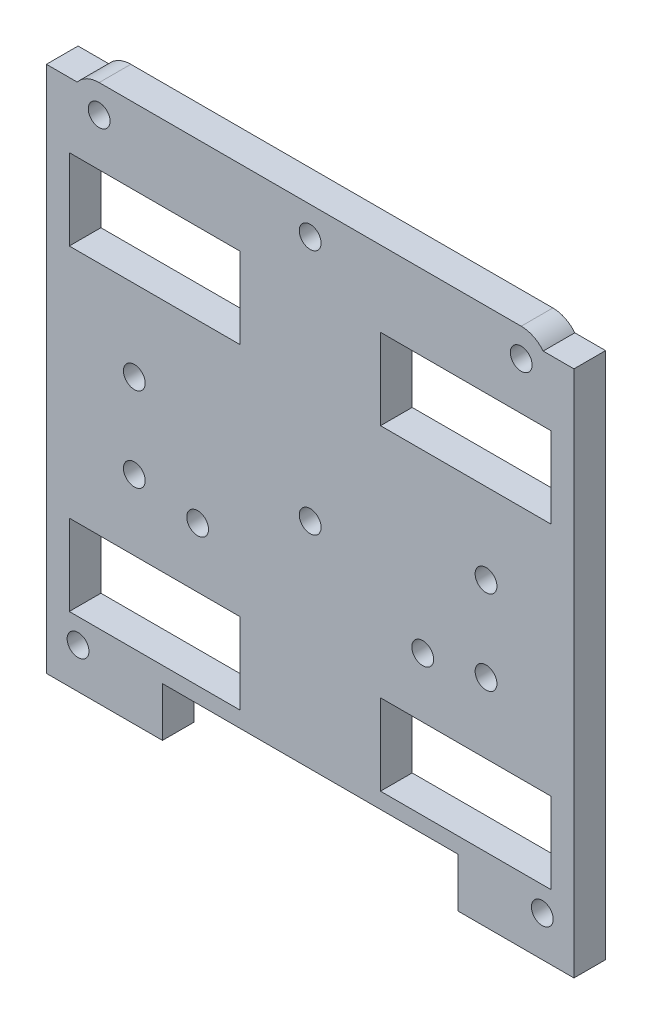
SolidWorks part; units mm, degrees
ref_plane "Front Plane" through (0, 0, 0) normal (0, 0, 1) x (1, 0, 0)
ref_plane "Top Plane" through (0, 0, 0) normal (0, 1, 0) x (1, 0, 0)
ref_plane "Right Plane" through (0, 0, 0) normal (1, 0, 0) x (0, 0, -1)
sketch "Sketch1" plane through (0, 0, 0) normal (0, 0, 1) x (1, 0, 0)
  line L0 (0, -37.5) -> (0, 37.5) construction
  line L1 (-47.5, -37.5) -> (47.5, -37.5)
  line L2 (-47.5, -37.5) -> (-47.5, 37.5)
  line L3 (-47.5, 37.5) -> (47.5, 37.5)
  line L4 (47.5, -37.5) -> (47.5, 37.5)
  line L5 (-47.5, -37.5) -> (47.5, 37.5) construction
  line L6 (-47.5, 37.5) -> (47.5, -37.5) construction
  line L7 (-47.5, 0) -> (47.5, 0) construction
  line L8 (-47.5, 22.5) -> (47.5, 22.5) construction
  line L9 (34.25, 16.75) -> (10, 28.25) construction
  line L10 (-34.25, 28.25) -> (-10, 28.25)
  line L11 (-34.25, 28.25) -> (-34.25, 16.75)
  line L12 (-34.25, 16.75) -> (-10, 16.75)
  line L13 (-10, 28.25) -> (-10, 16.75)
  line L14 (-34.25, 28.25) -> (-10, 16.75) construction
  line L15 (-34.25, 16.75) -> (-10, 28.25) construction
  line L16 (34.25, 28.25) -> (10, 16.75) construction
  line L17 (10, 28.25) -> (10, 16.75)
  line L18 (34.25, 16.75) -> (10, 16.75)
  line L19 (34.25, 28.25) -> (34.25, 16.75)
  line L20 (34.25, 28.25) -> (10, 28.25)
  line L21 (34.25, -28.25) -> (10, -16.75) construction
  line L22 (-34.25, -16.75) -> (-10, -28.25) construction
  line L23 (-34.25, -28.25) -> (-10, -16.75) construction
  line L24 (34.25, -16.75) -> (10, -28.25) construction
  line L25 (34.25, -28.25) -> (10, -28.25)
  line L26 (34.25, -28.25) -> (34.25, -16.75)
  line L27 (34.25, -16.75) -> (10, -16.75)
  line L28 (10, -28.25) -> (10, -16.75)
  line L29 (-10, -28.25) -> (-10, -16.75)
  line L30 (-34.25, -16.75) -> (-10, -16.75)
  line L31 (-34.25, -28.25) -> (-34.25, -16.75)
  line L32 (-34.25, -28.25) -> (-10, -28.25)
  point P0 (0, 0)
  point P12 (-22.125, 22.5)
  point P21 (22.125, 22.5)
  point P30 (22.125, -22.5)
  point P31 (-22.125, -22.5)
  dimension "D1" = 95
  dimension "D2" = 75
  dimension "D3" = 22.5
  dimension "D4" = 24.25
  dimension "D5" = 11.5
  dimension "D6" = 10
extrude "Boss-Extrude1" add sketch "Sketch1" along normal blind 4.5
sketch "Sketch8" plane through (0, 0, 4.5) normal (0, 0, 1) x (1, 0, 0)
  line L0 (-47.5, 37.5) -> (-47.5, -37.5) construction
  line L1 (47.5, -37.5) -> (47.5, 37.5) construction
  circle A0 centre (-47.5, 29.5) radius 8
  circle A1 centre (47.5, 29.5) radius 8
  dimension "D1" = 16
extrude "Boss-Extrude2" [suppressed] add sketch "Sketch8" against normal through all
sketch "Sketch2" plane through (0, 0, 4.5) normal (0, 0, 1) x (1, 0, 0)
  line L0 (0, -37.5) -> (0, 37.5) construction
  line L1 (-47.5, -37.5) -> (47.5, -37.5) construction
  line L2 (47.5, 37.5) -> (-47.5, 37.5) construction
  line L3 (-47.5, 0) -> (47.5, 0) construction
  line L4 (-47.5, 37.5) -> (-47.5, -37.5) construction
  line L5 (47.5, -37.5) -> (47.5, 37.5) construction
  line L6 (-40, 0) -> (40, 0) construction
  line L7 (-30, 35) -> (30, 35) construction
  circle A0 centre (-30, 35) radius 1.55
  circle A1 centre (30, 35) radius 1.55
  circle A2 centre (40, 0) radius 1.55
  circle A3 centre (-40, 0) radius 1.55
  circle A4 centre (0, 35) radius 1.55
  dimension "D1" = 3.1
  dimension "D7" = 3.1
  dimension "D8" = 3.1
  dimension "D9" = 3.1
  dimension "D2" = 30
  dimension "D3" = 35
  dimension "D4" = 80
  dimension "D5" = 40
  dimension "D6" = 0
extrude "screwHoles" cut sketch "Sketch2" against normal through all
sketch "Sketch3" plane through (0, 0, 4.5) normal (0, 0, 1) x (1, 0, 0)
  line L0 (-47.5, -20) -> (26.0486, -20) construction
  line L1 (-47.5, 37.5) -> (-47.5, -37.5) construction
  line L3 (0, 37.5) -> (0, -37.5) construction
  line L4 (47.5, 37.5) -> (-47.5, 37.5) construction
  line L5 (-47.5, -37.5) -> (47.5, -37.5) construction
  line L6 (19.1, -22.35) -> (8.9, -17.65) construction
  line L7 (-19.1, -17.65) -> (-8.9, -17.65)
  line L8 (-19.1, -17.65) -> (-19.1, -22.35)
  line L9 (-19.1, -22.35) -> (-8.9, -22.35)
  line L10 (-8.9, -17.65) -> (-8.9, -22.35)
  line L11 (-19.1, -17.65) -> (-8.9, -22.35) construction
  line L12 (-19.1, -22.35) -> (-8.9, -17.65) construction
  line L13 (19.1, -17.65) -> (8.9, -22.35) construction
  line L14 (8.9, -17.65) -> (8.9, -22.35)
  line L15 (19.1, -22.35) -> (8.9, -22.35)
  line L16 (19.1, -17.65) -> (19.1, -22.35)
  line L17 (19.1, -17.65) -> (8.9, -17.65)
  line L18 (-47.5, 37.5) -> (-47.5, -37.5) construction
  point P2 (-47.5, 0)
  point P12 (-14, -20)
  point P21 (14, -20)
  dimension "D1" = 10.2
  dimension "D2" = 4.7
  dimension "D3" = 14
  dimension "D4" = 20
extrude "BeltClamp" [suppressed] cut sketch "Sketch3" against normal through all
sketch "Sketch4" plane through (0, 0, 4.5) normal (0, 0, 1) x (1, 0, 0)
  line L0 (-47.5, 0) -> (47.5, 0) construction
  line L1 (-47.5, 37.5) -> (-47.5, -37.5) construction
  line L2 (47.5, -37.5) -> (47.5, 37.5) construction
  line L3 (0, 0) -> (0, 33.45) construction
  line L4 (-30.1, 2.35) -> (-19.9, 2.35)
  line L5 (-30.1, 2.35) -> (-30.1, -2.35)
  line L6 (-30.1, -2.35) -> (-19.9, -2.35)
  line L7 (-19.9, 2.35) -> (-19.9, -2.35)
  line L8 (-30.1, 2.35) -> (-19.9, -2.35) construction
  line L9 (-30.1, -2.35) -> (-19.9, 2.35) construction
  line L10 (30.1, -2.35) -> (19.9, 2.35) construction
  line L11 (30.1, 2.35) -> (19.9, -2.35) construction
  line L12 (19.9, 2.35) -> (19.9, -2.35)
  line L13 (30.1, -2.35) -> (19.9, -2.35)
  line L14 (30.1, 2.35) -> (30.1, -2.35)
  line L15 (30.1, 2.35) -> (19.9, 2.35)
  line L16 (-30.1, -2.35) -> (-19.9, 2.35) construction
  circle A0 centre (-40, 0) radius 1.55 construction
  circle A1 centre (0, 35) radius 1.55 construction
  circle A2 centre (0, 0) radius 1.55
  point P6 (-25, 0)
  point P22 (25, 0)
  dimension "D1" = 10.2
  dimension "D2" = 4.7
  dimension "D5" = 3.1
  dimension "D3" = 0
  dimension "D4" = 25
extrude "Cut-Extrude3" cut sketch "Sketch4" against normal through all
sketch "Sketch5" plane through (0, 0, 4.5) normal (0, 0, 1) x (1, 0, 0)
  line L0 (-47.5, -9.75) -> (47.5, -9.75) construction
  line L1 (-47.5, 37.5) -> (-47.5, -37.5) construction
  line L2 (47.5, -37.5) -> (47.5, 37.5) construction
  line L4 (0, -37.5) -> (0, 37.5) construction
  line L5 (-47.5, -37.5) -> (47.5, -37.5) construction
  line L6 (47.5, 37.5) -> (-47.5, 37.5) construction
  line L7 (-30.65, -14.85) -> (-35.35, -4.65) construction
  line L8 (30.65, -4.65) -> (35.35, -4.65)
  line L9 (30.65, -4.65) -> (30.65, -14.85)
  line L10 (30.65, -14.85) -> (35.35, -14.85)
  line L11 (35.35, -4.65) -> (35.35, -14.85)
  line L12 (30.65, -4.65) -> (35.35, -14.85) construction
  line L13 (30.65, -14.85) -> (35.35, -4.65) construction
  line L14 (-30.65, -4.65) -> (-35.35, -14.85) construction
  line L15 (-35.35, -4.65) -> (-35.35, -14.85)
  line L16 (-30.65, -14.85) -> (-35.35, -14.85)
  line L17 (-30.65, -4.65) -> (-30.65, -14.85)
  line L18 (-30.65, -4.65) -> (-35.35, -4.65)
  line L19 (33, -9.75) -> (33, -37.5) construction
  line L20 (-33, -9.75) -> (-33, -37.5) construction
  line L21 (-33, -31.75) -> (33, -31.75) construction
  circle A0 centre (33, -31.75) radius 1.55
  circle A1 centre (-33, -31.75) radius 1.55
  point P15 (33, -9.75)
  point P24 (-33, -9.75)
  dimension "D5" = 3.1
  dimension "D2" = 10.2
  dimension "D3" = 4.7
  dimension "D4" = 33
  dimension "D6" = 22
  dimension "D1" = 9.75
extrude "Cut-Extrude4" cut sketch "Sketch5" against normal through all
sketch "Sketch9" plane through (0, 0, 4.5) normal (0, 0, 1) x (1, 0, 0)
  line L0 (47.5, 37.5) -> (-47.5, 37.5) construction
  line L1 (0, 37.5) -> (0, -37.5) construction
  line L2 (-47.5, -37.5) -> (47.5, -37.5) construction
  line L3 (50.5, 35) -> (45.5, 35) construction
  line L4 (-50.5, 35) -> (-45.5, 35) construction
  circle A0 centre (-30, 35) radius 4
  circle A1 centre (-30, 35) radius 1.55
  circle A2 centre (-30, 35) radius 1.55 construction
  circle A3 centre (30, 35) radius 1.55
  circle A4 centre (30, 35) radius 4
  point P17 (0, -37.5)
  dimension "D1" = 8
extrude "Boss-Extrude3" add sketch "Sketch9" against normal through all
sketch "Sketch10" plane through (0, 0, 4.5) normal (0, 0, 1) x (1, 0, 0)
  line L0 (-60, 37.5) -> (-37.5, 37.5)
  line L1 (-37.5, 37.5) -> (-37.5, -37.5)
  line L2 (-47.5, -37.5) -> (47.5, -37.5) construction
  line L3 (-37.5, -37.5) -> (-60, -37.5)
  line L4 (-60, -37.5) -> (-60, 37.5)
  line L5 (0, 37.5) -> (0, -37.5) construction
  line L6 (26.8775, 37.5) -> (-26.8775, 37.5) construction
  line L7 (60, -37.5) -> (60, 37.5)
  line L8 (37.5, -37.5) -> (60, -37.5)
  line L9 (37.5, 37.5) -> (37.5, -37.5)
  line L10 (60, 37.5) -> (37.5, 37.5)
  line L11 (-60, -37.5) -> (-60, 37.5)
  line L12 (-33.1225, 37.5) -> (-47.5, 37.5) construction
  line M3 (47.5, -37.5) -> (47.5, 37.5)
  line M7 (-47.5, 37.5) -> (-47.5, -37.5)
  line M8 (-47.5, -37.5) -> (47.5, -37.5)
  dimension "D3" = 0
  dimension "D1" = 75
  dimension "D2" = 60
extrude "Cut-Extrude5" cut sketch "Sketch10" against normal through all contours L1 L0 M7 M8 | L10 L9 M3 M8 region at (42.5, 0, 4.5) region at (-42.5, 0, 4.5)
sketch "Sketch11" plane through (0, 0, 4.5) normal (0, 0, 1) x (1, 0, 0)
  line L0 (-30, 39) -> (30, 39)
  line L1 (30, 39) -> (26.8775, 37.5)
  line L2 (26.8775, 37.5) -> (-26.8775, 37.5)
  line L3 (-26.8775, 37.5) -> (-30, 39)
  arc A0 (-26.8775, 37.5) -> (-33.1225, 37.5) centre (-30, 35) ccw construction
  arc A1 (33.1225, 37.5) -> (26.8775, 37.5) centre (30, 35) ccw construction
extrude "Boss-Extrude4" add sketch "Sketch11" against normal through all
sketch "Sketch12" plane through (0, 0, 4.5) normal (0, 0, 1) x (1, 0, 0)
  line L0 (-37.5, -8.25) -> (37.5, -8.25) construction
  line L1 (-37.5, 37.5) -> (-37.5, -37.5) construction
  line L2 (37.5, 37.5) -> (37.5, -37.5) construction
  line L3 (0, 0) -> (0, -37.5) construction
  line L4 (-37.5, -37.5) -> (37.5, -37.5) construction
  circle A0 centre (-16, -8.25) radius 1.55
  circle A1 centre (16, -8.25) radius 1.55
  dimension "D2" = 3.1
  dimension "D1" = 16
  dimension "D3" = 8.25
extrude "FanBraceScrews" cut sketch "Sketch12" against normal through all
sketch "Sketch13" plane through (0, 0, 4.5) normal (0, 0, 1) x (1, 0, 0)
  line L0 (-37.5, -37.5) -> (37.5, -37.5) construction
  line L1 (-21, -44.5) -> (21, -44.5)
  line L2 (-21, -44.5) -> (-21, -30.5)
  line L3 (-21, -30.5) -> (21, -30.5)
  line L4 (21, -44.5) -> (21, -30.5)
  line L5 (-21, -44.5) -> (21, -30.5) construction
  line L6 (-21, -30.5) -> (21, -44.5) construction
  point P0 (0, -37.5)
  dimension "D1" = 42
  dimension "D2" = 7
extrude "Cut-Extrude7" cut sketch "Sketch13" against normal through all
sketch "Sketch14" plane through (0, 0, 4.5) normal (0, 0, 1) x (1, 0, 0)
  line L0 (16, -9.8) -> (16, 3.75) construction
  line L1 (0, 0) -> (0, -40.3958) construction
  line L2 (-16, -9.8) -> (-16, 3.75) construction
  circle A0 centre (16, -8.25) radius 1.55 construction
  circle A1 centre (16, 3.75) radius 1.55
  circle A2 centre (-16, 3.75) radius 1.55
  dimension "D2" = 3.1
  dimension "D1" = 12
extrude "Cut-Extrude8" [suppressed] cut sketch "Sketch14" against normal through all
sketch "Sketch15" plane through (0, 0, 4.5) normal (0, 0, 1) x (1, 0, 0)
  line L0 (-25, 5.25) -> (-25, -6.75) construction
  line L2 (0, 0) -> (0, -11.0705) construction
  line L3 (16, -8.3509) -> (25, -6.75) construction
  line L4 (25, 5.25) -> (25, -6.75) construction
  circle A0 centre (-25, 5.25) radius 1.55
  circle A1 centre (-25, -6.75) radius 1.55
  circle A2 centre (25, -6.75) radius 1.55
  circle A3 centre (25, 5.25) radius 1.55
  circle A5 centre (-16, -8.25) radius 1.55 construction
  dimension "D1" = 12
  dimension "D3" = 3.1
  dimension "D4" = 3.1
  dimension "D2" = 25
  dimension "D5" = 1.5
extrude "BeltClipScrews" cut sketch "Sketch15" against normal through all
sketch "Sketch16" plane through (0, 0, 4.5) normal (0, 0, 1) x (1, 0, 0)
  line L0 (0, 0) -> (0, -11.3016) construction
  line L1 (-30.1, 2.35) -> (-19.9, 2.35)
  line L2 (-30.1, 2.35) -> (-30.1, -2.35)
  line L3 (-30.1, -2.35) -> (-19.9, -2.35)
  line L4 (-19.9, 2.35) -> (-19.9, -2.35)
  line L5 (-35.35, -4.65) -> (-30.65, -4.65)
  line L6 (-35.35, -4.65) -> (-35.35, -14.85)
  line L7 (-35.35, -14.85) -> (-30.65, -14.85)
  line L8 (-30.65, -4.65) -> (-30.65, -14.85)
  line L9 (30.65, -4.65) -> (30.65, -14.85)
  line L10 (35.35, -14.85) -> (30.65, -14.85)
  line L11 (35.35, -4.65) -> (35.35, -14.85)
  line L12 (35.35, -4.65) -> (30.65, -4.65)
  line L13 (19.9, 2.35) -> (19.9, -2.35)
  line L14 (30.1, -2.35) -> (19.9, -2.35)
  line L15 (30.1, 2.35) -> (30.1, -2.35)
  line L16 (30.1, 2.35) -> (19.9, 2.35)
  line L17 (-30.65, -4.65) -> (-30.65, -14.85)
extrude "Boss-Extrude5" add sketch "Sketch16" against normal through all contours L8 L5 L6 L7 | L4 L1 L2 L3 | L15 L16 L13 L14 | L11 L12 L9 L10 region at (-25, 0, 4.5) region at (-33, -9.75, 4.5) region at (33, -9.75, 4.5) region at (25, 0, 4.5)
equation "\"X-ROD-SPACING\"=45"
equation "\"Y-ROD-SPACING\"=75"
equation "\"Z-ROD-SPACING\"=17.5"
equation "\"Y-BED-OFFSET\"=2"
equation "\"Y-BED-ROD-INSET\"=3.5"
equation "\"Y-BED-SCREW-SPACING\"=209"
equation "\"Y-BED-SCREW-CUTOUT-SLOT-HEIGHT\"=2"
equation "\"T-SLOT-NUT-FILLET-RADIUS\"=0.25"
equation "\"T-SLOT-SCREW-SHAFT-RADIUS\"=1.75"
equation "\"T-SLOT-SCREW-SHAFT-CUTOUT-LENGTH\"=10.5"
equation "\"T-SLOT-NUT-DEPTH\"=4.2"
equation "\"T-SLOT-NUT-WIDTH\"=3"
equation "\"T-SLOT-NUT-END-DISTANCE\"=8"
equation "\"ACRYLIC-THICKNESS\"=10"
equation "\"ACRYLIC-THICKNESS2\"=4.5"
equation "\"ACRYLIC-TAB-CUTOUT-SIZE\"=\"ACRYLIC-THICKNESS\"+\"ACRYLIC-TAB-TOLERANCE\"*2"
equation "\"ACRYLIC-TAB-WIDTH\"=\"ACRYLIC-THICKNESS\""
equation "\"ACRYLIC-M3-HOLE\"=3.1"
equation "\"SMOOTHROD-CAP-SCREW-DISTANCE\"=20"
equation "\"FRAME-WIDTH-INNER\"=370"
equation "\"NEMA17-HOLE-SPACING\"=31"
equation "\"NEMA17-CENTRAL-CUTOUT\"=22.5"
equation "\"Z-BRACKET-REACH\"=55"
equation "\"Z-ROD-INSET\"=16"
equation "\"TOP-BRACKET-SPACING\"=40"
equation "\"SMOOTHROD-X-LENGTH\"=350"
equation "\"SMOOTHROD-Y-LENGTH\"=350"
equation "\"SMOOTHROD-Z-LENGTH\"=350"
equation "\"SMOOTHROD-TIGHTENING-HEADROOM\"=.25"
equation "\"LEADSCREW-Z-LENGTH\"=300"
equation "\"SCREW-LENGTH-FRAME\"=\"ACRYLIC-THICKNESS\" + 10"
equation "\"SCREW-LENGTH-MOTOR\"=\"ACRYLIC-THICKNESS\" + 5"
equation "\"SCREW-HEAD-RADIUS\"=6"
equation "\"PRINTED-X-SMOOTHROD-DIAMETER\"=8.2"
equation "\"PRINTED-X-SMOOTHROD-CUTOUT\"=10"
equation "\"PRINTED-X-BASE-HEIGHT\"=10"
equation "\"PRINTED-LM8UU-CUTOUT-SIZE\"=15.25"
equation "\"PRINTED-LM8UU-CUTOUT-LENGTH\"=24.5"
equation "\"PRINTED-X-IDLER-HEIGHT\"=16"
equation "\"PSU-MOUNTING-WIDTH\"=95"
equation "\"PSU-MOUNTING-HEIGHT\"=177"
equation "\"Y-BELT-TO-ROD-DISTANCE\"=20"
equation "\"SPOOL-HOLDER-ROD-SPACING\"=150"
equation "\"D3@Sketch1\"=\"X-ROD-SPACING\"/2"
equation "\"D4@Sketch1\"=\"ACRYLIC-X-CARRIAGE-LM8UU-CUTOUT-WIDTH\""
equation "\"D1@Boss-Extrude1\"=\"ACRYLIC-THICKNESS2\""
equation "\"D1@Sketch2\"=\"ACRYLIC-M3-HOLE\""
equation "\"D1@Sketch3\"=\"ACRYLIC-TAB-CUTOUT-SIZE\""
equation "\"D2@Sketch3\"=\"ACRYLIC-THICKNESS2\"+\"ACRYLIC-TAB-TOLERANCE\"*2"
equation "\"ACRYLIC-X-CARRIAGE-WIDTH\"=55"
equation "\"ACRYLIC-X-CARRIAGE-HEIGHT\"=75"
equation "\"D2@Sketch1\"=\"ACRYLIC-X-CARRIAGE-HEIGHT\""
equation "\"ACRYLIC-X-CARRIAGE-CENTER-TAB-SPACING\"=14"
equation "\"D3@Sketch3\"=\"ACRYLIC-X-CARRIAGE-CENTER-TAB-SPACING\""
equation "\"SCREW-LENGTH-EXTRUDER\"=28"
equation "\"ACRYLIC-X-CARRIAGE-SCREW-SPACING-X\"=15"
equation "\"ACRYLIC-X-CARRIAGE-SCREW-SPACING-Y\"=33"
equation "\"D1@Sketch4\"=\"ACRYLIC-TAB-CUTOUT-SIZE\""
equation "\"D2@Sketch4\"=\"ACRYLIC-THICKNESS2\"+\"ACRYLIC-TAB-TOLERANCE\"*2"
equation "\"D2@Sketch5\"=\"ACRYLIC-TAB-CUTOUT-SIZE\""
equation "\"D3@Sketch5\"=\"ACRYLIC-THICKNESS2\"+\"ACRYLIC-TAB-TOLERANCE\"*2"
equation "\"ACRYLIC-X-CARRIAGE-EXTRUDER-SHELF-DEPTH\"=\"ACRYLIC-X-CARRIAGE-EXTRUDER-OFFSET\" + 28"
equation "\"ACRYLIC-X-CARRIAGE-EXTRUDER-BRACE-SPACING\"=23"
equation "\"D4@Sketch5\"=\"ACRYLIC-X-CARRIAGE-DUAL-MOUNT-BRACE-WIDTH\""
equation "\"D1@Sketch5\"=\"ACRYLIC-THICKNESS2\"/2 + 7.5"
equation "\"D4@Sketch2\"=\"ACRYLIC-X-CARRIAGE-DUAL-MOUNT-SCREW-WIDTH\"*2"
equation "\"D5@Sketch2\"=\"ACRYLIC-X-CARRIAGE-DUAL-MOUNT-SCREW-WIDTH\""
equation "\"D7@Sketch2\"=\"ACRYLIC-M3-HOLE\""
equation "\"D8@Sketch2\"=\"ACRYLIC-M3-HOLE\""
equation "\"ACRYLIC-X-CARRIAGE-LM8UU-CUTOUT-WIDTH\"=24.25"
equation "\"ACRYLIC-TAB-TOLERANCE\"=.1"
equation "\"ACRYLIC-X-CARRIAGE-EXTRUDER-OFFSET\"=26"
equation "\"ACRYLIC-X-CARRIAGE-EXTRUDER-ANGLE\"=90"
equation "\"ACRYLIC-X-CARRIAGE-EXTRUDER-BRACE-TAB-OFFSET\"=20"
equation "\"ACRYLIC-X-CARRIAGE-EXTRUDER-BRACE-HEIGHT\"=35"
equation "\"ACRYLIC-X-CARRIAGE-EXTRUDER-BRACE-SCREW-SPACING\"=22"
equation "\"D5@Sketch5\"=\"ACRYLIC-M3-HOLE\""
equation "\"ACRYLIC-X-CARRIAGE-DUAL-WIDTH-MULTIPLIER\"=1.65"
equation "\"ACRYLIC-X-CARRIAGE-DUAL-HOTEND-SPACING\"=42"
equation "\"ACRYLIC-X-CARRIAGE-DUAL-WIDTH\"=75"
equation "\"ACRYLIC-X-CARRIAGE-DUAL-HOTEND-SEPARATION\"=36"
equation "\"ACRYLIC-X-CARRIAGE-DUAL-MOUNT-PLATE-DEPTH\"=75"
equation "\"ACRYLIC-X-CARRIAGE-DUAL-MOUNT-BRACE-WIDTH\"=33"
equation "\"ACRYLIC-X-CARRIAGE-DUAL-MOUNT-SCREW-WIDTH\"=40"
equation "\"D9@Sketch2\"=\"ACRYLIC-M3-HOLE\""
equation "\"ACRYLIC-X-CARRIAGE-LM8UU-CUTOUT-HEIGHT\"=11.5"
equation "\"D5@Sketch1\"=\"ACRYLIC-X-CARRIAGE-LM8UU-CUTOUT-HEIGHT\""
equation "\"D1@Sketch10\"=\"ACRYLIC-X-CARRIAGE-DUAL-WIDTH\""
equation "\"D5@Sketch4\"=\"ACRYLIC-M3-HOLE\""
equation "\"D2@Sketch12\"=\"ACRYLIC-M3-HOLE\""
equation "\"D3@Sketch12\"=\"ACRYLIC-THICKNESS2\"/2 + 6"
equation "\"D2@Sketch14\"=\"ACRYLIC-M3-HOLE\""
equation "\"D3@Sketch15\"=\"ACRYLIC-M3-HOLE\""
equation "\"D4@Sketch15\"=\"ACRYLIC-M3-HOLE\""
